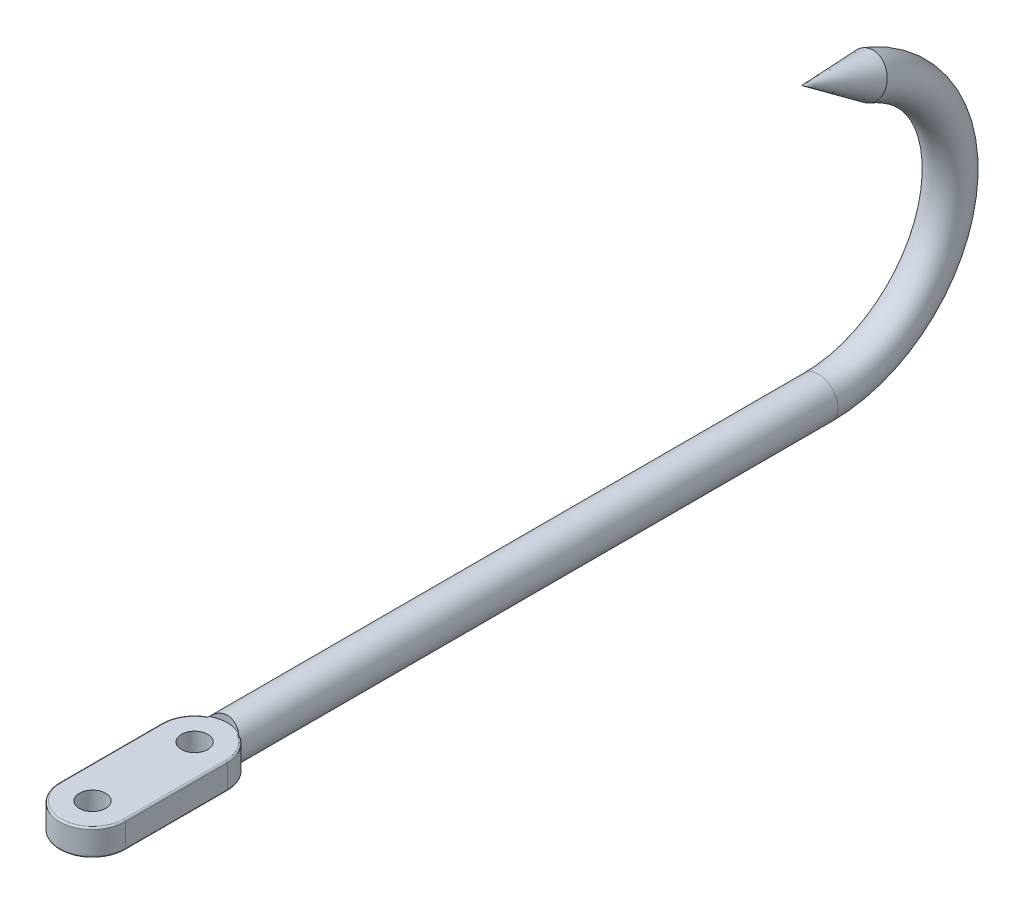
SolidWorks part; units mm, degrees
ref_plane "Front Plane" through (0, 0, 0) normal (0, 0, 1) x (1, 0, 0)
ref_plane "Top Plane" through (0, 0, 0) normal (0, 1, 0) x (1, 0, 0)
ref_plane "Right Plane" through (0, 0, 0) normal (1, 0, 0) x (0, 0, -1)
sketch "Sketch1" plane through (0, 0, 0) normal (0, 0, 1) x (1, 0, 0)
  circle A0 centre (0, 0) radius 3
  dimension "D1" = 6
sketch "Sketch10" plane through (0, 0, 0) normal (1, 0, 0) x (0, 0, -1)
  line L0 (0, 0) -> (90.6945, 0)
  line L1 (97.5349, 38.7939) -> (88.1379, 42.2141)
  arc A0 (90.6945, 0) -> (97.5349, 38.7939) centre (90.6945, 20) ccw
  dimension "D1" = 20
sweep "Sweep2" add profiles "Sketch1" path "Sketch10"
sketch "Sketch4" plane through (0, 0, 0) normal (0, 1, 0) x (1, 0, 0)
  line L1 (-5, -4) -> (5, -4)
  line L2 (-5, -4) -> (-5, -19.5)
  line L3 (-5, -19.5) -> (5, -19.5)
  line L4 (5, -4) -> (5, -19.5)
  circle A0 centre (0, -4) radius 5
  circle A1 centre (0, -19.5) radius 5
  dimension "D5" = 10
  dimension "D6" = 10
  dimension "D7" = 4
  dimension "D1" = 15.5
  dimension "D2" = 10
  dimension "D3" = 0
  dimension "D4" = 5
extrude "Boss-Extrude1" add sketch "Sketch4" along normal blind 2 and the other way blind 2 contours A1 L4 A0 L2 | L3 A1 | L3 A1 | L1 A0 | L1 A0 region at (0, 0, 1.8779) region at (0, 0, 11.75) region at (0, 0, 6.1221) region at (0, 0, 17.3779) region at (0, 0, 21.6221)
sketch "Sketch5" plane through (0, -2, 0) normal (0, -1, 0) x (-1, 0, 0)
  circle A0 centre (0, -19.5) radius 2
  circle A1 centre (0, -4) radius 2
  arc A2 (-5, -19.5) -> (5, -19.5) centre (0, -19.5) ccw construction
  point P4 (0, -24.5)
  dimension "D1" = 4
  dimension "D2" = 4
  dimension "D3" = 5
  dimension "D4" = 5
  dimension "D5" = 5
  dimension "D6" = 15.5
extrude "Cut-Extrude1" cut sketch "Sketch5" against normal up to next
sketch "Sketch7" plane through (0, -2, 0) normal (0, -1, 0) x (1, 0, 0)
  line L0 (5, 4) -> (5, 19.5) construction
  line L1 (-5, 4) -> (5, 4)
  arc A0 (-5, 4) -> (5, 4) centre (0, 4) ccw
  arc A1 (-5, 4) -> (-2.2361, -0.4721) centre (0, 4) ccw construction
extrude "Cut-Extrude3" cut sketch "Sketch7" along normal up to next
sketch "Sketch9" plane through (0, 2, 0) normal (0, 1, 0) x (1, 0, 0)
  line L0 (5, -4) -> (5, -19.5) construction
  line L1 (-5, -4) -> (-5, -19.5) construction
  line L2 (5, -4) -> (-5, -4)
  arc A0 (5, -4) -> (-5, -4) centre (0, -4) ccw
  arc A1 (5, -4) -> (2.2361, 0.4721) centre (0, -4) ccw construction
extrude "Cut-Extrude4" cut sketch "Sketch9" along normal up to next
fillet "Fillet2" radius 0.25 10 edges at (-4.2533, 2, 1.3713) (4.2533, 2, 1.3713) (5, 2, 11.75) (0, 2, 24.5) (-4.2533, -2, 1.3713) (4.2533, -2, 1.3713) (5, -2, 11.75) (0, -2, 24.5) (-5, 2, 11.75) (-5, -2, 11.75)
chamfer "Chamfer2" distance 3 angle 74 1 edges at (3, 42.2141, -88.1379) first distance on face at (3, 42.2141, -88.1379)
